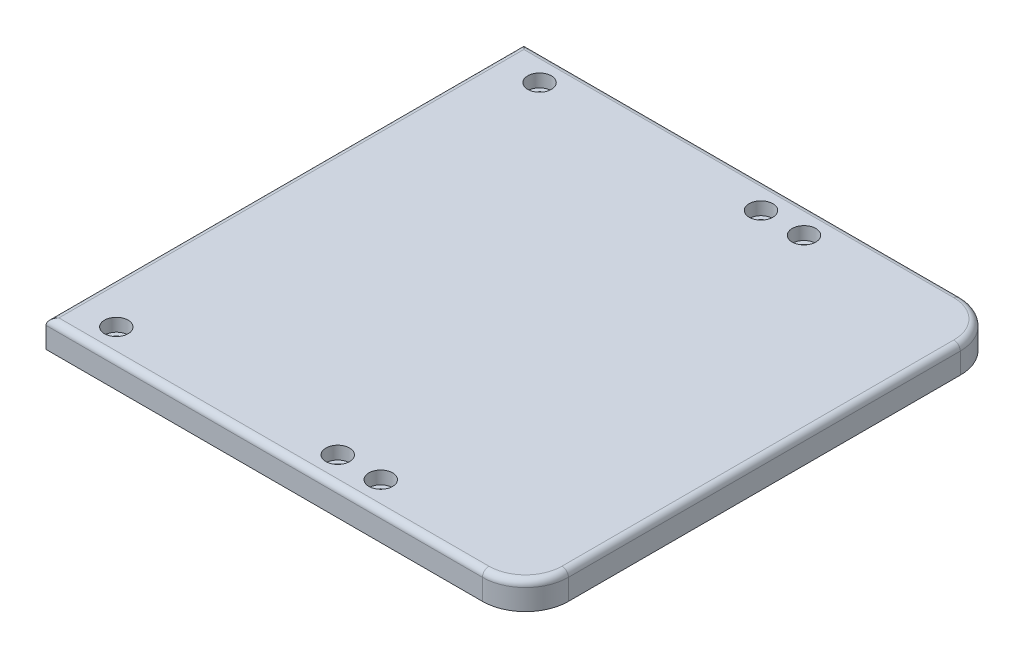
SolidWorks part; units mm, degrees
ref_plane "Front Plane" through (0, 0, 0) normal (0, 0, 1) x (1, 0, 0)
ref_plane "Top Plane" through (0, 0, 0) normal (0, 1, 0) x (1, 0, 0)
ref_plane "Right Plane" through (0, 0, 0) normal (1, 0, 0) x (0, 0, -1)
sketch "Sketch2" plane through (0, 0, 0) normal (0, 1, 0) x (1, 0, 0)
  line L1 (-111.5, 111.125) -> (111.5, 111.125)
  line L2 (-111.5, 111.125) -> (-111.5, -111.125)
  line L3 (-111.5, -111.125) -> (111.5, -111.125)
  line L4 (111.5, 111.125) -> (111.5, -111.125)
  line L5 (-111.5, 111.125) -> (111.5, -111.125) construction
  line L6 (-111.5, -111.125) -> (111.5, 111.125) construction
  point P0 (0, 0)
  dimension "D2" = 222.25
  dimension "D1" = 223
extrude "Boss-Extrude1" add sketch "Sketch2" along normal blind 12.7
fillet "Fillet6" radius 20 2 edges at (111.5, 6.35, -111.125) (111.5, 6.35, 111.125)
fillet "Fillet5" radius 3 6 edges at (-10, 12.7, 111.125) (-111.5, 12.7, 0) (-10, 12.7, -111.125) (111.5, 12.7, 0) (105.6421, 12.7, 105.2671) (105.6421, 12.7, -105.2671)
sketch "Sketch4" plane through (0, 12.7, 0) normal (0, 1, 0) x (1, 0, 0)
  line L0 (0, 0) -> (-45.9035, 0) construction
  line L1 (0, 0) -> (0, -26.5712) construction
  line L2 (91.5, -111.125) -> (-111.5, -111.125) construction
  line L3 (-111.5, -111.125) -> (-111.5, 111.125) construction
  line L4 (111.5, 91.125) -> (111.5, -91.125) construction
  point P0 (-91.5, -98.425)
  point P9 (11.5, 98.425)
  point P10 (31.5, -98.425)
  point P13 (31.5, 98.425)
  point P14 (-91.5, 98.425)
  point P21 (11.5, -98.425)
  dimension "D1" = 12.7
  dimension "D2" = 20
  dimension "D3" = 80
  dimension "D4" = 20
hole_wizard "CBORE for M6 SHCS1" positions "Sketch5" profile "Sketch6" counterbore size "M6" standard "ANSI Metric" end condition up to next
sketch "Sketch5" plane through (0, 12.7, 0) normal (0, 1, 0) x (1, 0, 0)
  point P0 (-91.5, -98.425)
  point P3 (31.5, -98.425)
  point P6 (31.5, 98.425)
  point P9 (-91.5, 98.425)
  point P12 (11.5, -98.425)
  point P15 (11.5, 98.425)
sketch "Sketch6" plane through (-91.5, 12.7, 98.425) normal (1, 0, 0) x (0, 0, 1)
  line L0 (0, 0) -> (0, 12.7)
  line L1 (0, 12.7) -> (3.3, 12.7)
  line L3 (3.3, 12.7) -> (3.3, 6)
  line L4 (3.3, 6) -> (5.5, 6)
  line L5 (5.5, 6) -> (5.5, 0)
  line L7 (5.5, 0) -> (0, 0)
  line L11 (0, -6.35) -> (0, 107.95) construction
  dimension "Thru Hole Dia." = 6.6
  dimension "Thru Hole Depth" = 12.7
  dimension "C'Bore Dia." = 11
  dimension "C'Bore Depth" = 6
equation "\"Length\"=250"
equation "\"Width\"=222.25"
equation "\"D2@Sketch2\"=\"Width\""
